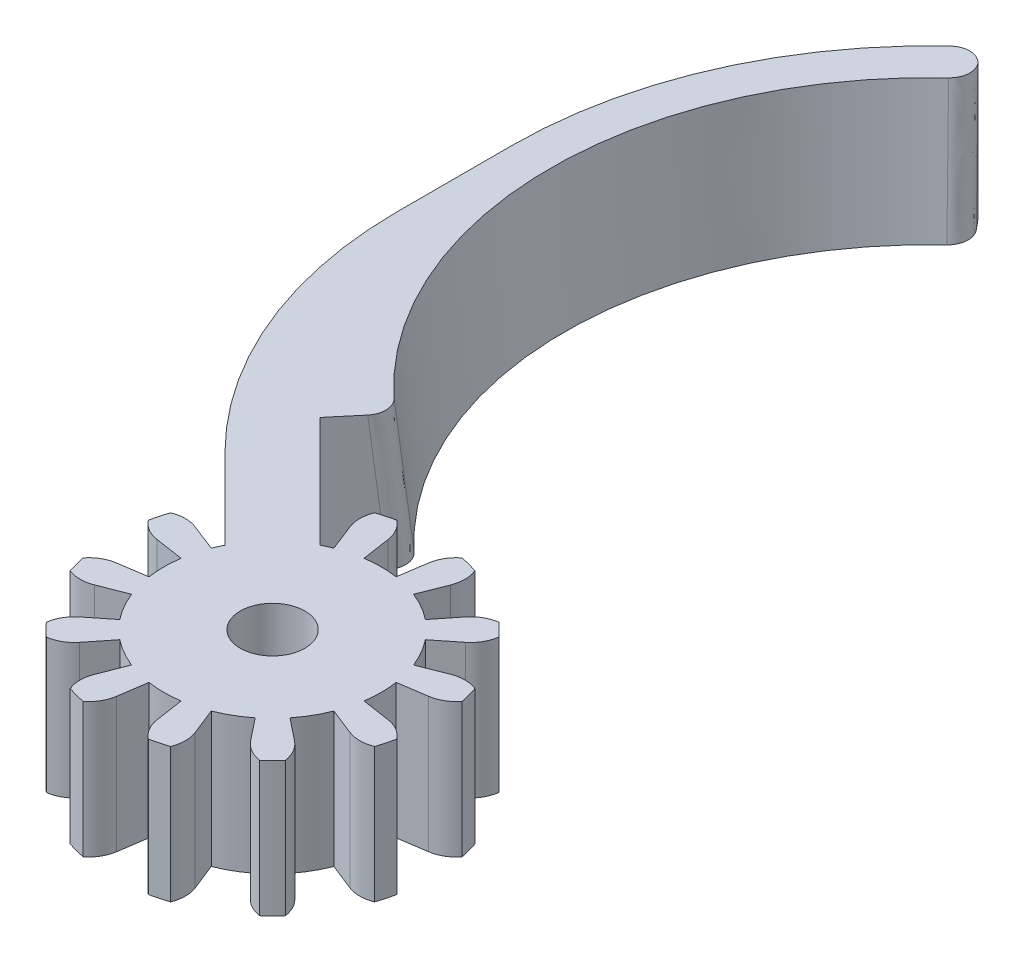
SolidWorks part; units mm, degrees
ref_plane "Plan de face" through (0, 0, 0) normal (0, 0, 1) x (1, 0, 0)
ref_plane "Plan de dessus" through (0, 0, 0) normal (0, 1, 0) x (1, 0, 0)
ref_plane "Plan de droite" through (0, 0, 0) normal (1, 0, 0) x (0, 0, -1)
sketch "Esquisse1" plane through (0, 0, 0) normal (0, 1, 0) x (1, 0, 0)
  line L0 (0, 0) -> (0, 27.3284) construction
  line L1 (-38.1202, 0) -> (19.7056, 0) construction
  line L2 (8.75, 40) -> (-53.1888, 40) construction
  line L3 (8.75, 40) -> (-13.9541, 12.9423) construction
  line L4 (8.75, 40) -> (-15.7208, 69.1632) construction
  line L5 (-22.25, 47.3971) -> (-22.25, -30.6529) construction
  line L6 (0, 0) -> (-33.9162, 33.9162) construction
  line L7 (-13.1703, 9.6348) -> (-7.1971, 3.6616)
  line L8 (-11.8794, 15.4149) -> (-3.6616, 7.1971)
  line L9 (-22.25, 40) -> (-22.25, 31.5551)
  line L10 (0, 0) -> (3.5575, 13.2769) construction
  line L11 (0, 0) -> (7.0447, 12.2018) construction
  line L12 (0, 0) -> (4.3209, 13.1034) construction
  line L13 (0, 0) -> (5.1162, 12.9881) construction
  line L14 (3.7383, 9.4903) -> (2.9595, 7.5131)
  line L15 (1.5077, 10.088) -> (1.1936, 7.9863)
  line L16 (6.3496, 7.9826) -> (5.0268, 6.3196)
  line L17 (7.9826, 6.3496) -> (6.3196, 5.0268)
  line L18 (9.4903, 3.7383) -> (7.5131, 2.9595)
  line L19 (10.088, 1.5077) -> (7.9863, 1.1936)
  line L20 (10.088, -1.5077) -> (7.9863, -1.1936)
  line L21 (9.4903, -3.7383) -> (7.5131, -2.9595)
  line L22 (7.9826, -6.3496) -> (6.3196, -5.0268)
  line L23 (6.3496, -7.9826) -> (5.0268, -6.3196)
  line L24 (3.7383, -9.4903) -> (2.9595, -7.5131)
  line L25 (1.5077, -10.088) -> (1.1936, -7.9863)
  line L26 (-1.5077, -10.088) -> (-1.1936, -7.9863)
  line L27 (-3.7383, -9.4903) -> (-2.9595, -7.5131)
  line L28 (-6.3496, -7.9826) -> (-5.0268, -6.3196)
  line L29 (-7.9826, -6.3496) -> (-6.3196, -5.0268)
  line L30 (-9.4903, -3.7383) -> (-7.5131, -2.9595)
  line L31 (-10.088, -1.5077) -> (-7.9863, -1.1936)
  line L32 (-10.088, 1.5077) -> (-7.9863, 1.1936)
  line L33 (-9.4903, 3.7383) -> (-7.5131, 2.9595)
  line L34 (-17.25, 40) -> (-17.25, -30.6529) construction
  line L36 (-3.7383, 9.4903) -> (-2.9595, 7.5131)
  line L37 (-1.5077, 10.088) -> (-1.1936, 7.9863)
  line L38 (-7.9826, 6.3496) -> (-6.3196, 5.0268) [skipped]
  line L39 (-6.3496, 7.9826) -> (-5.0268, 6.3196) [skipped]
  line L40 (-11.8794, 15.4149) -> (-7.9625, 20.0828)
  line L41 (-10.1877, 62.5691) -> (-7.9625, 59.9172)
  line L42 (8.75, 40) -> (8.75, 0) construction
  circle A0 centre (0, 0) radius 11.9 construction
  circle A1 centre (0, 0) radius 10.2 construction
  circle A2 centre (0, 0) radius 8.075 construction
  circle A3 centre (8.75, 40) radius 25 construction
  arc A4 (-7.9625, 59.9172) -> (-7.9625, 20.0828) centre (8.75, 40) ccw
  arc A5 (-22.25, 40) -> (-12.3581, 62.7035) centre (8.75, 40) cw
  arc A7 (3.7266, 11.3014) -> (3.7383, 9.4903) centre (1.4762, 10.3813) cw
  arc A8 (3.7266, 11.3014) -> (2.4233, 11.6506) centre (0, 0) ccw
  arc A9 (4.0375, 6.9932) -> (2.9595, 7.5131) centre (0, 0) ccw
  arc A10 (0, 8.075) -> (1.1936, 7.9863) centre (0, 0) cw
  arc A11 (2.4233, 11.6506) -> (1.5077, 10.088) centre (3.9122, 9.7286) ccw
  arc A12 (4.0375, 6.9932) -> (5.0268, 6.3196) centre (0, 0) cw
  arc A13 (7.924, 8.8781) -> (6.3496, 7.9826) centre (8.2524, 6.4691) ccw
  arc A14 (8.8781, 7.924) -> (7.924, 8.8781) centre (0, 0) ccw
  arc A15 (8.8781, 7.924) -> (7.9826, 6.3496) centre (6.4691, 8.2524) cw
  arc A16 (6.9932, 4.0375) -> (6.3196, 5.0268) centre (0, 0) ccw
  arc A17 (6.9932, 4.0375) -> (7.5131, 2.9595) centre (0, 0) cw
  arc A18 (11.3014, 3.7266) -> (9.4903, 3.7383) centre (10.3813, 1.4762) ccw
  arc A19 (11.6506, 2.4233) -> (11.3014, 3.7266) centre (0, 0) ccw
  arc A20 (11.6506, 2.4233) -> (10.088, 1.5077) centre (9.7286, 3.9122) cw
  arc A21 (8.075, 0) -> (7.9863, 1.1936) centre (0, 0) ccw
  arc A22 (8.075, 0) -> (7.9863, -1.1936) centre (0, 0) cw
  arc A23 (11.6506, -2.4233) -> (10.088, -1.5077) centre (9.7286, -3.9122) ccw
  arc A24 (11.3014, -3.7266) -> (11.6506, -2.4233) centre (0, 0) ccw
  arc A25 (11.3014, -3.7266) -> (9.4903, -3.7383) centre (10.3813, -1.4762) cw
  arc A26 (6.9932, -4.0375) -> (7.5131, -2.9595) centre (0, 0) ccw
  arc A27 (6.9932, -4.0375) -> (6.3196, -5.0268) centre (0, 0) cw
  arc A28 (8.8781, -7.924) -> (7.9826, -6.3496) centre (6.4691, -8.2524) ccw
  arc A29 (7.924, -8.8781) -> (8.8781, -7.924) centre (0, 0) ccw
  arc A30 (7.924, -8.8781) -> (6.3496, -7.9826) centre (8.2524, -6.4691) cw
  arc A31 (4.0375, -6.9932) -> (5.0268, -6.3196) centre (0, 0) ccw
  arc A32 (4.0375, -6.9932) -> (2.9595, -7.5131) centre (0, 0) cw
  arc A33 (3.7266, -11.3014) -> (3.7383, -9.4903) centre (1.4762, -10.3813) ccw
  arc A34 (2.4233, -11.6506) -> (3.7266, -11.3014) centre (0, 0) ccw
  arc A35 (2.4233, -11.6506) -> (1.5077, -10.088) centre (3.9122, -9.7286) cw
  arc A36 (0, -8.075) -> (1.1936, -7.9863) centre (0, 0) ccw
  arc A37 (0, -8.075) -> (-1.1936, -7.9863) centre (0, 0) cw
  arc A38 (-2.4233, -11.6506) -> (-1.5077, -10.088) centre (-3.9122, -9.7286) ccw
  arc A39 (-3.7266, -11.3014) -> (-2.4233, -11.6506) centre (0, 0) ccw
  arc A40 (-3.7266, -11.3014) -> (-3.7383, -9.4903) centre (-1.4762, -10.3813) cw
  arc A41 (-4.0375, -6.9932) -> (-2.9595, -7.5131) centre (0, 0) ccw
  arc A42 (-4.0375, -6.9932) -> (-5.0268, -6.3196) centre (0, 0) cw
  arc A43 (-7.924, -8.8781) -> (-6.3496, -7.9826) centre (-8.2524, -6.4691) ccw
  arc A44 (-8.8781, -7.924) -> (-7.924, -8.8781) centre (0, 0) ccw
  arc A45 (-8.8781, -7.924) -> (-7.9826, -6.3496) centre (-6.4691, -8.2524) cw
  arc A46 (-6.9932, -4.0375) -> (-6.3196, -5.0268) centre (0, 0) ccw
  arc A47 (-6.9932, -4.0375) -> (-7.5131, -2.9595) centre (0, 0) cw
  arc A48 (-11.3014, -3.7266) -> (-9.4903, -3.7383) centre (-10.3813, -1.4762) ccw
  arc A49 (-11.6506, -2.4233) -> (-11.3014, -3.7266) centre (0, 0) ccw
  arc A50 (-11.6506, -2.4233) -> (-10.088, -1.5077) centre (-9.7286, -3.9122) cw
  arc A51 (-8.075, 0) -> (-7.9863, -1.1936) centre (0, 0) ccw
  arc A52 (-8.075, 0) -> (-7.9863, 1.1936) centre (0, 0) cw
  arc A53 (-11.6506, 2.4233) -> (-10.088, 1.5077) centre (-9.7286, 3.9122) ccw
  arc A54 (-11.3014, 3.7266) -> (-11.6506, 2.4233) centre (0, 0) ccw
  arc A55 (-11.3014, 3.7266) -> (-9.4903, 3.7383) centre (-10.3813, 1.4762) cw
  arc A56 (-2.9595, 7.5131) -> (-3.6616, 7.1971) centre (0, 0) ccw
  arc A57 (-7.5131, 2.9595) -> (-7.1971, 3.6616) centre (0, 0) cw
  arc A60 (-13.1703, 9.6348) -> (-22.25, 31.5551) centre (8.75, 31.5551) cw
  arc A61 (-12.3581, 62.7035) -> (-10.1877, 62.5691) centre (-11.3368, 61.6049) cw
  arc A63 (-3.7266, 11.3014) -> (-3.7383, 9.4903) centre (-1.4762, 10.3813) ccw
  arc A64 (-2.4233, 11.6506) -> (-3.7266, 11.3014) centre (0, 0) ccw
  arc A65 (-2.4233, 11.6506) -> (-1.5077, 10.088) centre (-3.9122, 9.7286) cw
  arc A66 (0, 8.075) -> (-1.1936, 7.9863) centre (0, 0) ccw
  arc A67 (-8.8781, 7.924) -> (-7.9826, 6.3496) centre (-6.4691, 8.2524) ccw [skipped]
  arc A68 (-7.924, 8.8781) -> (-8.8781, 7.924) centre (0, 0) ccw [skipped]
  arc A69 (-7.924, 8.8781) -> (-6.3496, 7.9826) centre (-8.2524, 6.4691) cw [skipped]
  arc A70 (-6.9932, 4.0375) -> (-6.3196, 5.0268) centre (0, 0) cw [skipped]
  arc A71 (-4.0375, 6.9932) -> (-5.0268, 6.3196) centre (0, 0) ccw [skipped]
  arc A72 (-4.0375, 6.9932) -> (-2.9595, 7.5131) centre (0, 0) cw [skipped]
  arc A73 (-6.9932, 4.0375) -> (-7.5131, 2.9595) centre (0, 0) ccw [skipped]
  point P72 (0, 0)
  point P135 (-17.25, 20.2855)
  point P138 (-22.25, 18.7145)
  point P155 (-11.1764, 63.7474)
  point P169 (-10.855, 16.6356)
  point P176 (-17.25, 23.2668)
  dimension "D1" = 50
  dimension "D2" = 50
  dimension "D5" = 20.4
  dimension "D6" = 23.8
  dimension "D7" = 16.15
  dimension "D11" = 26
  dimension "D12" = 5
  dimension "D17" = 12
  dimension "D18" = 5
  dimension "D20" = 1.5
  dimension "D3" = 40
  dimension "D4" = 50
  dimension "D9" = 45
  dimension "D10" = 5
  dimension "D13" = 8.75
  dimension "D14" = 3.25
  dimension "D15" = 6.5
  dimension "D16" = 15
extrude "Boss.-Extru.1" add sketch "Esquisse1" along normal blind 10
chamfer "Chanfrein1" distance 20 angle 6.03 1 edges at (-17.25, 10, -40)
fillet "Congé1" radius 1.5 2 edges at (-8.981, 5, -61.131) (-8.981, 5, -18.869)
sketch "Esquisse3" plane through (0, 10, 0) normal (0, 1, 0) x (1, 0, 0)
  line L26 (-22.25, 40) -> (-22.25, 31.5551)
  line L27 (-13.1703, 9.6348) -> (-7.1971, 3.6616)
  line L28 (-7.5131, 2.9595) -> (-9.4903, 3.7383)
  line L29 (-10.088, 1.5077) -> (-7.9863, 1.1936)
  line L30 (-7.9863, -1.1936) -> (-10.088, -1.5077)
  line L31 (-9.4903, -3.7383) -> (-7.5131, -2.9595)
  line L32 (-6.3196, -5.0268) -> (-7.9826, -6.3496)
  line L33 (-6.3496, -7.9826) -> (-5.0268, -6.3196)
  line L34 (-2.9595, -7.5131) -> (-3.7383, -9.4903)
  line L35 (-1.5077, -10.088) -> (-1.1936, -7.9863)
  line L36 (1.1936, -7.9863) -> (1.5077, -10.088)
  line L37 (3.7383, -9.4903) -> (2.9595, -7.5131)
  line L38 (5.0268, -6.3196) -> (6.3496, -7.9826)
  line L39 (7.9826, -6.3496) -> (6.3196, -5.0268)
  line L40 (7.5131, -2.9595) -> (9.4903, -3.7383)
  line L41 (10.088, -1.5077) -> (7.9863, -1.1936)
  line L42 (7.9863, 1.1936) -> (10.088, 1.5077)
  line L43 (9.4903, 3.7383) -> (7.5131, 2.9595)
  line L44 (6.3196, 5.0268) -> (7.9826, 6.3496)
  line L45 (6.3496, 7.9826) -> (5.0268, 6.3196)
  line L46 (2.9595, 7.5131) -> (3.7383, 9.4903)
  line L47 (1.5077, 10.088) -> (1.1936, 7.9863)
  line L48 (-1.1936, 7.9863) -> (-1.5077, 10.088)
  line L49 (-3.7383, 9.4903) -> (-2.9595, 7.5131)
  line L50 (-3.6616, 7.1971) -> (-11.8794, 15.4149)
  line L51 (-11.8794, 15.4149) -> (-10.2656, 17.3381)
  line L52 (-22.25, 40) -> (-22.25, 31.5551)
  line L53 (-13.1703, 9.6348) -> (-7.1971, 3.6616)
  line L54 (-7.5131, 2.9595) -> (-9.4903, 3.7383)
  line L55 (-10.088, 1.5077) -> (-7.9863, 1.1936)
  line L56 (-7.9863, -1.1936) -> (-10.088, -1.5077)
  line L57 (-9.4903, -3.7383) -> (-7.5131, -2.9595)
  line L58 (-6.3196, -5.0268) -> (-7.9826, -6.3496)
  line L59 (-6.3496, -7.9826) -> (-5.0268, -6.3196)
  line L60 (-2.9595, -7.5131) -> (-3.7383, -9.4903)
  line L61 (-1.5077, -10.088) -> (-1.1936, -7.9863)
  line L62 (1.1936, -7.9863) -> (1.5077, -10.088)
  line L63 (3.7383, -9.4903) -> (2.9595, -7.5131)
  line L64 (5.0268, -6.3196) -> (6.3496, -7.9826)
  line L65 (7.9826, -6.3496) -> (6.3196, -5.0268)
  line L66 (7.5131, -2.9595) -> (9.4903, -3.7383)
  line L67 (10.088, -1.5077) -> (7.9863, -1.1936)
  line L68 (7.9863, 1.1936) -> (10.088, 1.5077)
  line L69 (9.4903, 3.7383) -> (7.5131, 2.9595)
  line L70 (6.3196, 5.0268) -> (7.9826, 6.3496)
  line L71 (6.3496, 7.9826) -> (5.0268, 6.3196)
  line L72 (2.9595, 7.5131) -> (3.7383, 9.4903)
  line L73 (1.5077, 10.088) -> (1.1936, 7.9863)
  line L74 (-1.1936, 7.9863) -> (-1.5077, 10.088)
  line L75 (-3.7383, 9.4903) -> (-2.9595, 7.5131)
  line L76 (-3.6616, 7.1971) -> (-11.8794, 15.4149)
  line L77 (-11.8794, 15.4149) -> (-10.2656, 17.3381)
  circle A0 centre (0, 0) radius 2.4
  arc A49 (-10.3884, 60.5923) -> (-10.3884, 19.4077) centre (8.75, 40) ccw
  arc A50 (-10.2275, 62.6146) -> (-12.3581, 62.7035) centre (-11.3368, 61.6049) ccw
  arc A51 (-12.3581, 62.7035) -> (-22.25, 40) centre (8.75, 40) ccw
  arc A52 (-22.25, 31.5551) -> (-13.1703, 9.6348) centre (8.75, 31.5551) ccw
  arc A53 (-7.1971, 3.6616) -> (-7.5131, 2.9595) centre (0, 0) ccw
  arc A54 (-9.4903, 3.7383) -> (-11.3014, 3.7266) centre (-10.3813, 1.4762) ccw
  arc A55 (-11.3014, 3.7266) -> (-11.6506, 2.4233) centre (0, 0) ccw
  arc A56 (-11.6506, 2.4233) -> (-10.088, 1.5077) centre (-9.7286, 3.9122) ccw
  arc A57 (-7.9863, 1.1936) -> (-7.9863, -1.1936) centre (0, 0) ccw
  arc A58 (-10.088, -1.5077) -> (-11.6506, -2.4233) centre (-9.7286, -3.9122) ccw
  arc A59 (-11.6506, -2.4233) -> (-11.3014, -3.7266) centre (0, 0) ccw
  arc A60 (-11.3014, -3.7266) -> (-9.4903, -3.7383) centre (-10.3813, -1.4762) ccw
  arc A61 (-7.5131, -2.9595) -> (-6.3196, -5.0268) centre (0, 0) ccw
  arc A62 (-7.9826, -6.3496) -> (-8.8781, -7.924) centre (-6.4691, -8.2524) ccw
  arc A63 (-8.8781, -7.924) -> (-7.924, -8.8781) centre (0, 0) ccw
  arc A64 (-7.924, -8.8781) -> (-6.3496, -7.9826) centre (-8.2524, -6.4691) ccw
  arc A65 (-5.0268, -6.3196) -> (-2.9595, -7.5131) centre (0, 0) ccw
  arc A66 (-3.7383, -9.4903) -> (-3.7266, -11.3014) centre (-1.4762, -10.3813) ccw
  arc A67 (-3.7266, -11.3014) -> (-2.4233, -11.6506) centre (0, 0) ccw
  arc A68 (-2.4233, -11.6506) -> (-1.5077, -10.088) centre (-3.9122, -9.7286) ccw
  arc A69 (-1.1936, -7.9863) -> (1.1936, -7.9863) centre (0, 0) ccw
  arc A70 (1.5077, -10.088) -> (2.4233, -11.6506) centre (3.9122, -9.7286) ccw
  arc A71 (2.4233, -11.6506) -> (3.7266, -11.3014) centre (0, 0) ccw
  arc A72 (3.7266, -11.3014) -> (3.7383, -9.4903) centre (1.4762, -10.3813) ccw
  arc A73 (2.9595, -7.5131) -> (5.0268, -6.3196) centre (0, 0) ccw
  arc A74 (6.3496, -7.9826) -> (7.924, -8.8781) centre (8.2524, -6.4691) ccw
  arc A75 (7.924, -8.8781) -> (8.8781, -7.924) centre (0, 0) ccw
  arc A76 (8.8781, -7.924) -> (7.9826, -6.3496) centre (6.4691, -8.2524) ccw
  arc A77 (6.3196, -5.0268) -> (7.5131, -2.9595) centre (0, 0) ccw
  arc A78 (9.4903, -3.7383) -> (11.3014, -3.7266) centre (10.3813, -1.4762) ccw
  arc A79 (11.3014, -3.7266) -> (11.6506, -2.4233) centre (0, 0) ccw
  arc A80 (11.6506, -2.4233) -> (10.088, -1.5077) centre (9.7286, -3.9122) ccw
  arc A81 (7.9863, -1.1936) -> (7.9863, 1.1936) centre (0, 0) ccw
  arc A82 (10.088, 1.5077) -> (11.6506, 2.4233) centre (9.7286, 3.9122) ccw
  arc A83 (11.6506, 2.4233) -> (11.3014, 3.7266) centre (0, 0) ccw
  arc A84 (11.3014, 3.7266) -> (9.4903, 3.7383) centre (10.3813, 1.4762) ccw
  arc A85 (7.5131, 2.9595) -> (6.3196, 5.0268) centre (0, 0) ccw
  arc A86 (7.9826, 6.3496) -> (8.8781, 7.924) centre (6.4691, 8.2524) ccw
  arc A87 (8.8781, 7.924) -> (7.924, 8.8781) centre (0, 0) ccw
  arc A88 (7.924, 8.8781) -> (6.3496, 7.9826) centre (8.2524, 6.4691) ccw
  arc A89 (5.0268, 6.3196) -> (2.9595, 7.5131) centre (0, 0) ccw
  arc A90 (3.7383, 9.4903) -> (3.7266, 11.3014) centre (1.4762, 10.3813) ccw
  arc A91 (3.7266, 11.3014) -> (2.4233, 11.6506) centre (0, 0) ccw
  arc A92 (2.4233, 11.6506) -> (1.5077, 10.088) centre (3.9122, 9.7286) ccw
  arc A93 (1.1936, 7.9863) -> (-1.1936, 7.9863) centre (0, 0) ccw
  arc A94 (-1.5077, 10.088) -> (-2.4233, 11.6506) centre (-3.9122, 9.7286) ccw
  arc A95 (-2.4233, 11.6506) -> (-3.7266, 11.3014) centre (0, 0) ccw
  arc A96 (-3.7266, 11.3014) -> (-3.7383, 9.4903) centre (-1.4762, 10.3813) ccw
  arc A97 (-2.9595, 7.5131) -> (-3.6616, 7.1971) centre (0, 0) ccw
  arc A98 (-10.3884, 60.5923) -> (-10.3884, 19.4077) centre (8.75, 40) ccw
  arc A99 (-10.2275, 62.6146) -> (-12.3581, 62.7035) centre (-11.3368, 61.6049) ccw
  arc A100 (-12.3581, 62.7035) -> (-22.25, 40) centre (8.75, 40) ccw
  arc A101 (-22.25, 31.5551) -> (-13.1703, 9.6348) centre (8.75, 31.5551) ccw
  arc A102 (-7.1971, 3.6616) -> (-7.5131, 2.9595) centre (0, 0) ccw
  arc A103 (-9.4903, 3.7383) -> (-11.3014, 3.7266) centre (-10.3813, 1.4762) ccw
  arc A104 (-11.3014, 3.7266) -> (-11.6506, 2.4233) centre (0, 0) ccw
  arc A105 (-11.6506, 2.4233) -> (-10.088, 1.5077) centre (-9.7286, 3.9122) ccw
  arc A106 (-7.9863, 1.1936) -> (-7.9863, -1.1936) centre (0, 0) ccw
  arc A107 (-10.088, -1.5077) -> (-11.6506, -2.4233) centre (-9.7286, -3.9122) ccw
  arc A108 (-11.6506, -2.4233) -> (-11.3014, -3.7266) centre (0, 0) ccw
  arc A109 (-11.3014, -3.7266) -> (-9.4903, -3.7383) centre (-10.3813, -1.4762) ccw
  arc A110 (-7.5131, -2.9595) -> (-6.3196, -5.0268) centre (0, 0) ccw
  arc A111 (-7.9826, -6.3496) -> (-8.8781, -7.924) centre (-6.4691, -8.2524) ccw
  arc A112 (-8.8781, -7.924) -> (-7.924, -8.8781) centre (0, 0) ccw
  arc A113 (-7.924, -8.8781) -> (-6.3496, -7.9826) centre (-8.2524, -6.4691) ccw
  arc A114 (-5.0268, -6.3196) -> (-2.9595, -7.5131) centre (0, 0) ccw
  arc A115 (-3.7383, -9.4903) -> (-3.7266, -11.3014) centre (-1.4762, -10.3813) ccw
  arc A116 (-3.7266, -11.3014) -> (-2.4233, -11.6506) centre (0, 0) ccw
  arc A117 (-2.4233, -11.6506) -> (-1.5077, -10.088) centre (-3.9122, -9.7286) ccw
  arc A118 (-1.1936, -7.9863) -> (1.1936, -7.9863) centre (0, 0) ccw
  arc A119 (1.5077, -10.088) -> (2.4233, -11.6506) centre (3.9122, -9.7286) ccw
  arc A120 (2.4233, -11.6506) -> (3.7266, -11.3014) centre (0, 0) ccw
  arc A121 (3.7266, -11.3014) -> (3.7383, -9.4903) centre (1.4762, -10.3813) ccw
  arc A122 (2.9595, -7.5131) -> (5.0268, -6.3196) centre (0, 0) ccw
  arc A123 (6.3496, -7.9826) -> (7.924, -8.8781) centre (8.2524, -6.4691) ccw
  arc A124 (7.924, -8.8781) -> (8.8781, -7.924) centre (0, 0) ccw
  arc A125 (8.8781, -7.924) -> (7.9826, -6.3496) centre (6.4691, -8.2524) ccw
  arc A126 (6.3196, -5.0268) -> (7.5131, -2.9595) centre (0, 0) ccw
  arc A127 (9.4903, -3.7383) -> (11.3014, -3.7266) centre (10.3813, -1.4762) ccw
  arc A128 (11.3014, -3.7266) -> (11.6506, -2.4233) centre (0, 0) ccw
  arc A129 (11.6506, -2.4233) -> (10.088, -1.5077) centre (9.7286, -3.9122) ccw
  arc A130 (7.9863, -1.1936) -> (7.9863, 1.1936) centre (0, 0) ccw
  arc A131 (10.088, 1.5077) -> (11.6506, 2.4233) centre (9.7286, 3.9122) ccw
  arc A132 (11.6506, 2.4233) -> (11.3014, 3.7266) centre (0, 0) ccw
  arc A133 (11.3014, 3.7266) -> (9.4903, 3.7383) centre (10.3813, 1.4762) ccw
  arc A134 (7.5131, 2.9595) -> (6.3196, 5.0268) centre (0, 0) ccw
  arc A135 (7.9826, 6.3496) -> (8.8781, 7.924) centre (6.4691, 8.2524) ccw
  arc A136 (8.8781, 7.924) -> (7.924, 8.8781) centre (0, 0) ccw
  arc A137 (7.924, 8.8781) -> (6.3496, 7.9826) centre (8.2524, 6.4691) ccw
  arc A138 (5.0268, 6.3196) -> (2.9595, 7.5131) centre (0, 0) ccw
  arc A139 (3.7383, 9.4903) -> (3.7266, 11.3014) centre (1.4762, 10.3813) ccw
  arc A140 (3.7266, 11.3014) -> (2.4233, 11.6506) centre (0, 0) ccw
  arc A141 (2.4233, 11.6506) -> (1.5077, 10.088) centre (3.9122, 9.7286) ccw
  arc A142 (1.1936, 7.9863) -> (-1.1936, 7.9863) centre (0, 0) ccw
  arc A143 (-1.5077, 10.088) -> (-2.4233, 11.6506) centre (-3.9122, 9.7286) ccw
  arc A144 (-2.4233, 11.6506) -> (-3.7266, 11.3014) centre (0, 0) ccw
  arc A145 (-3.7266, 11.3014) -> (-3.7383, 9.4903) centre (-1.4762, 10.3813) ccw
  arc A146 (-2.9595, 7.5131) -> (-3.6616, 7.1971) centre (0, 0) ccw
  spline S2 degree 3 poles (904.1768, 2910.4144) (-208.0871, 144.2381) (-16.4538, 47.7772) (-10.0195, 61.1214) (-9.9874, 61.208) (-9.9391, 61.3864) (-9.9231, 61.4792) (-8.9721, 73.586) (-156.7275, 93.4089) (359.3029, -2911.4528) knots -19.517492 -19.517492 -19.517492 -19.517492 0.25 0.25 0.375 0.375 0.5 0.5 16.747829 16.747829 16.747829 16.747829 only from (-10.3884, 60.5923) to (-10.2275, 62.6146)
  spline S3 degree 3 poles (652.1757, 2936.6854) (-207.8805, 69.6069) (-14.5415, 4.1362) (-9.9582, 17.9249) (-9.9369, 18.0173) (-9.9119, 18.2055) (-9.9082, 18.3023) (-9.9192, 18.4923) (-9.9335, 18.5859) (-9.9802, 18.7706) (-10.0127, 18.8618) (-14.9397, 29.3716) (-143.2098, -13.6236) (1107.06, -2761.596) knots -18.632107 -18.632107 -18.632107 -18.632107 0.25 0.25 0.375 0.375 0.5 0.5 0.625 0.625 0.75 0.75 15.917753 15.917753 15.917753 15.917753 only from (-10.2656, 17.3381) to (-10.3884, 19.4077)
  spline S4 degree 3 poles (-10.3884, 60.5923) (-10.2513, 60.7197) (-10.1408, 60.8699) (-10.0195, 61.1214) (-9.9874, 61.208) (-9.9391, 61.3864) (-9.9231, 61.4792) (-9.8868, 61.9413) (-9.9986, 62.3184) (-10.2275, 62.6146) knots 0 0 0 0 0.25 0.25 0.375 0.375 0.5 0.5 1 1 1 1
  spline S5 degree 3 poles (-10.2656, 17.3381) (-10.142, 17.4854) (-10.0486, 17.6529) (-9.9582, 17.9249) (-9.9369, 18.0173) (-9.9119, 18.2055) (-9.9082, 18.3023) (-9.9192, 18.4923) (-9.9335, 18.5859) (-9.9802, 18.7706) (-10.0127, 18.8618) (-10.1335, 19.1195) (-10.2476, 19.2768) (-10.3884, 19.4077) knots 0 0 0 0 0.25 0.25 0.375 0.375 0.5 0.5 0.625 0.625 0.75 0.75 1 1 1 1
  dimension "D2" = 4.8
  dimension "D1" = 0
extrude "Enlèv. mat.-Extru.1" cut sketch "Esquisse3" against normal blind 4 contours A0
sketch "Esquisse4" plane through (0, 0, 0) normal (0, -1, 0) x (1, 0, 0)
  line L26 (-9.5857, -18.1484) -> (-11.8794, -15.4149)
  line L27 (-11.8794, -15.4149) -> (-3.6616, -7.1971)
  line L28 (-2.9595, -7.5131) -> (-3.7383, -9.4903)
  line L29 (-1.5077, -10.088) -> (-1.1936, -7.9863)
  line L30 (1.1936, -7.9863) -> (1.5077, -10.088)
  line L31 (3.7383, -9.4903) -> (2.9595, -7.5131)
  line L32 (5.0268, -6.3196) -> (6.3496, -7.9826)
  line L33 (7.9826, -6.3496) -> (6.3196, -5.0268)
  line L34 (7.5131, -2.9595) -> (9.4903, -3.7383)
  line L35 (10.088, -1.5077) -> (7.9863, -1.1936)
  line L36 (7.9863, 1.1936) -> (10.088, 1.5077)
  line L37 (9.4903, 3.7383) -> (7.5131, 2.9595)
  line L38 (6.3196, 5.0268) -> (7.9826, 6.3496)
  line L39 (6.3496, 7.9826) -> (5.0268, 6.3196)
  line L40 (2.9595, 7.5131) -> (3.7383, 9.4903)
  line L41 (1.5077, 10.088) -> (1.1936, 7.9863)
  line L42 (-1.1936, 7.9863) -> (-1.5077, 10.088)
  line L43 (-3.7383, 9.4903) -> (-2.9595, 7.5131)
  line L44 (-5.0268, 6.3196) -> (-6.3496, 7.9826)
  line L45 (-7.9826, 6.3496) -> (-6.3196, 5.0268)
  line L46 (-7.5131, 2.9595) -> (-9.4903, 3.7383)
  line L47 (-10.088, 1.5077) -> (-7.9863, 1.1936)
  line L48 (-7.9863, -1.1936) -> (-10.088, -1.5077)
  line L49 (-9.4903, -3.7383) -> (-7.5131, -2.9595)
  line L50 (-7.1971, -3.6616) -> (-13.1703, -9.6348)
  line L51 (-22.25, -31.5551) -> (-22.25, -40)
  line L52 (-9.5857, -18.1484) -> (-11.8794, -15.4149)
  line L53 (-11.8794, -15.4149) -> (-3.6616, -7.1971)
  line L54 (-2.9595, -7.5131) -> (-3.7383, -9.4903)
  line L55 (-1.5077, -10.088) -> (-1.1936, -7.9863)
  line L56 (1.1936, -7.9863) -> (1.5077, -10.088)
  line L57 (3.7383, -9.4903) -> (2.9595, -7.5131)
  line L58 (5.0268, -6.3196) -> (6.3496, -7.9826)
  line L59 (7.9826, -6.3496) -> (6.3196, -5.0268)
  line L60 (7.5131, -2.9595) -> (9.4903, -3.7383)
  line L61 (10.088, -1.5077) -> (7.9863, -1.1936)
  line L62 (7.9863, 1.1936) -> (10.088, 1.5077)
  line L63 (9.4903, 3.7383) -> (7.5131, 2.9595)
  line L64 (6.3196, 5.0268) -> (7.9826, 6.3496)
  line L65 (6.3496, 7.9826) -> (5.0268, 6.3196)
  line L66 (2.9595, 7.5131) -> (3.7383, 9.4903)
  line L67 (1.5077, 10.088) -> (1.1936, 7.9863)
  line L68 (-1.1936, 7.9863) -> (-1.5077, 10.088)
  line L69 (-3.7383, 9.4903) -> (-2.9595, 7.5131)
  line L70 (-5.0268, 6.3196) -> (-6.3496, 7.9826)
  line L71 (-7.9826, 6.3496) -> (-6.3196, 5.0268)
  line L72 (-7.5131, 2.9595) -> (-9.4903, 3.7383)
  line L73 (-10.088, 1.5077) -> (-7.9863, 1.1936)
  line L74 (-7.9863, -1.1936) -> (-10.088, -1.5077)
  line L75 (-9.4903, -3.7383) -> (-7.5131, -2.9595)
  line L76 (-7.1971, -3.6616) -> (-13.1703, -9.6348)
  line L77 (-22.25, -31.5551) -> (-22.25, -40)
  line L79 (-10.1877, -62.5691) -> (-9.5857, -61.8516)
  line L80 (-10.1877, -62.5691) -> (-9.5857, -61.8516)
  circle A0 centre (0, 0) radius 4
  arc A47 (-9.7065, -20.2161) -> (-9.7065, -59.7839) centre (8.75, -40) ccw
  arc A48 (-3.6616, -7.1971) -> (-2.9595, -7.5131) centre (0, 0) ccw
  arc A49 (-3.7383, -9.4903) -> (-3.7266, -11.3014) centre (-1.4762, -10.3813) ccw
  arc A50 (-3.7266, -11.3014) -> (-2.4233, -11.6506) centre (0, 0) ccw
  arc A51 (-2.4233, -11.6506) -> (-1.5077, -10.088) centre (-3.9122, -9.7286) ccw
  arc A52 (-1.1936, -7.9863) -> (1.1936, -7.9863) centre (0, 0) ccw
  arc A53 (1.5077, -10.088) -> (2.4233, -11.6506) centre (3.9122, -9.7286) ccw
  arc A54 (2.4233, -11.6506) -> (3.7266, -11.3014) centre (0, 0) ccw
  arc A55 (3.7266, -11.3014) -> (3.7383, -9.4903) centre (1.4762, -10.3813) ccw
  arc A56 (2.9595, -7.5131) -> (5.0268, -6.3196) centre (0, 0) ccw
  arc A57 (6.3496, -7.9826) -> (7.924, -8.8781) centre (8.2524, -6.4691) ccw
  arc A58 (7.924, -8.8781) -> (8.8781, -7.924) centre (0, 0) ccw
  arc A59 (8.8781, -7.924) -> (7.9826, -6.3496) centre (6.4691, -8.2524) ccw
  arc A60 (6.3196, -5.0268) -> (7.5131, -2.9595) centre (0, 0) ccw
  arc A61 (9.4903, -3.7383) -> (11.3014, -3.7266) centre (10.3813, -1.4762) ccw
  arc A62 (11.3014, -3.7266) -> (11.6506, -2.4233) centre (0, 0) ccw
  arc A63 (11.6506, -2.4233) -> (10.088, -1.5077) centre (9.7286, -3.9122) ccw
  arc A64 (7.9863, -1.1936) -> (7.9863, 1.1936) centre (0, 0) ccw
  arc A65 (10.088, 1.5077) -> (11.6506, 2.4233) centre (9.7286, 3.9122) ccw
  arc A66 (11.6506, 2.4233) -> (11.3014, 3.7266) centre (0, 0) ccw
  arc A67 (11.3014, 3.7266) -> (9.4903, 3.7383) centre (10.3813, 1.4762) ccw
  arc A68 (7.5131, 2.9595) -> (6.3196, 5.0268) centre (0, 0) ccw
  arc A69 (7.9826, 6.3496) -> (8.8781, 7.924) centre (6.4691, 8.2524) ccw
  arc A70 (8.8781, 7.924) -> (7.924, 8.8781) centre (0, 0) ccw
  arc A71 (7.924, 8.8781) -> (6.3496, 7.9826) centre (8.2524, 6.4691) ccw
  arc A72 (5.0268, 6.3196) -> (2.9595, 7.5131) centre (0, 0) ccw
  arc A73 (3.7383, 9.4903) -> (3.7266, 11.3014) centre (1.4762, 10.3813) ccw
  arc A74 (3.7266, 11.3014) -> (2.4233, 11.6506) centre (0, 0) ccw
  arc A75 (2.4233, 11.6506) -> (1.5077, 10.088) centre (3.9122, 9.7286) ccw
  arc A76 (1.1936, 7.9863) -> (-1.1936, 7.9863) centre (0, 0) ccw
  arc A77 (-1.5077, 10.088) -> (-2.4233, 11.6506) centre (-3.9122, 9.7286) ccw
  arc A78 (-2.4233, 11.6506) -> (-3.7266, 11.3014) centre (0, 0) ccw
  arc A79 (-3.7266, 11.3014) -> (-3.7383, 9.4903) centre (-1.4762, 10.3813) ccw
  arc A80 (-2.9595, 7.5131) -> (-5.0268, 6.3196) centre (0, 0) ccw
  arc A81 (-6.3496, 7.9826) -> (-7.924, 8.8781) centre (-8.2524, 6.4691) ccw
  arc A82 (-7.924, 8.8781) -> (-8.8781, 7.924) centre (0, 0) ccw
  arc A83 (-8.8781, 7.924) -> (-7.9826, 6.3496) centre (-6.4691, 8.2524) ccw
  arc A84 (-6.3196, 5.0268) -> (-7.5131, 2.9595) centre (0, 0) ccw
  arc A85 (-9.4903, 3.7383) -> (-11.3014, 3.7266) centre (-10.3813, 1.4762) ccw
  arc A86 (-11.3014, 3.7266) -> (-11.6506, 2.4233) centre (0, 0) ccw
  arc A87 (-11.6506, 2.4233) -> (-10.088, 1.5077) centre (-9.7286, 3.9122) ccw
  arc A88 (-7.9863, 1.1936) -> (-7.9863, -1.1936) centre (0, 0) ccw
  arc A89 (-10.088, -1.5077) -> (-11.6506, -2.4233) centre (-9.7286, -3.9122) ccw
  arc A90 (-11.6506, -2.4233) -> (-11.3014, -3.7266) centre (0, 0) ccw
  arc A91 (-11.3014, -3.7266) -> (-9.4903, -3.7383) centre (-10.3813, -1.4762) ccw
  arc A92 (-7.5131, -2.9595) -> (-7.1971, -3.6616) centre (0, 0) ccw
  arc A93 (-13.1703, -9.6348) -> (-22.25, -31.5551) centre (8.75, -31.5551) ccw
  arc A95 (-3.6616, -7.1971) -> (-2.9595, -7.5131) centre (0, 0) ccw
  arc A96 (-3.7383, -9.4903) -> (-3.7266, -11.3014) centre (-1.4762, -10.3813) ccw
  arc A97 (-3.7266, -11.3014) -> (-2.4233, -11.6506) centre (0, 0) ccw
  arc A98 (-2.4233, -11.6506) -> (-1.5077, -10.088) centre (-3.9122, -9.7286) ccw
  arc A99 (-1.1936, -7.9863) -> (1.1936, -7.9863) centre (0, 0) ccw
  arc A100 (1.5077, -10.088) -> (2.4233, -11.6506) centre (3.9122, -9.7286) ccw
  arc A101 (2.4233, -11.6506) -> (3.7266, -11.3014) centre (0, 0) ccw
  arc A102 (3.7266, -11.3014) -> (3.7383, -9.4903) centre (1.4762, -10.3813) ccw
  arc A103 (2.9595, -7.5131) -> (5.0268, -6.3196) centre (0, 0) ccw
  arc A104 (6.3496, -7.9826) -> (7.924, -8.8781) centre (8.2524, -6.4691) ccw
  arc A105 (7.924, -8.8781) -> (8.8781, -7.924) centre (0, 0) ccw
  arc A106 (8.8781, -7.924) -> (7.9826, -6.3496) centre (6.4691, -8.2524) ccw
  arc A107 (6.3196, -5.0268) -> (7.5131, -2.9595) centre (0, 0) ccw
  arc A108 (9.4903, -3.7383) -> (11.3014, -3.7266) centre (10.3813, -1.4762) ccw
  arc A109 (11.3014, -3.7266) -> (11.6506, -2.4233) centre (0, 0) ccw
  arc A110 (11.6506, -2.4233) -> (10.088, -1.5077) centre (9.7286, -3.9122) ccw
  arc A111 (7.9863, -1.1936) -> (7.9863, 1.1936) centre (0, 0) ccw
  arc A112 (10.088, 1.5077) -> (11.6506, 2.4233) centre (9.7286, 3.9122) ccw
  arc A113 (11.6506, 2.4233) -> (11.3014, 3.7266) centre (0, 0) ccw
  arc A114 (11.3014, 3.7266) -> (9.4903, 3.7383) centre (10.3813, 1.4762) ccw
  arc A115 (7.5131, 2.9595) -> (6.3196, 5.0268) centre (0, 0) ccw
  arc A116 (7.9826, 6.3496) -> (8.8781, 7.924) centre (6.4691, 8.2524) ccw
  arc A117 (8.8781, 7.924) -> (7.924, 8.8781) centre (0, 0) ccw
  arc A118 (7.924, 8.8781) -> (6.3496, 7.9826) centre (8.2524, 6.4691) ccw
  arc A119 (5.0268, 6.3196) -> (2.9595, 7.5131) centre (0, 0) ccw
  arc A120 (3.7383, 9.4903) -> (3.7266, 11.3014) centre (1.4762, 10.3813) ccw
  arc A121 (3.7266, 11.3014) -> (2.4233, 11.6506) centre (0, 0) ccw
  arc A122 (2.4233, 11.6506) -> (1.5077, 10.088) centre (3.9122, 9.7286) ccw
  arc A123 (1.1936, 7.9863) -> (-1.1936, 7.9863) centre (0, 0) ccw
  arc A124 (-1.5077, 10.088) -> (-2.4233, 11.6506) centre (-3.9122, 9.7286) ccw
  arc A125 (-2.4233, 11.6506) -> (-3.7266, 11.3014) centre (0, 0) ccw
  arc A126 (-3.7266, 11.3014) -> (-3.7383, 9.4903) centre (-1.4762, 10.3813) ccw
  arc A127 (-2.9595, 7.5131) -> (-5.0268, 6.3196) centre (0, 0) ccw
  arc A128 (-6.3496, 7.9826) -> (-7.924, 8.8781) centre (-8.2524, 6.4691) ccw
  arc A129 (-7.924, 8.8781) -> (-8.8781, 7.924) centre (0, 0) ccw
  arc A130 (-8.8781, 7.924) -> (-7.9826, 6.3496) centre (-6.4691, 8.2524) ccw
  arc A131 (-6.3196, 5.0268) -> (-7.5131, 2.9595) centre (0, 0) ccw
  arc A132 (-9.4903, 3.7383) -> (-11.3014, 3.7266) centre (-10.3813, 1.4762) ccw
  arc A133 (-11.3014, 3.7266) -> (-11.6506, 2.4233) centre (0, 0) ccw
  arc A134 (-11.6506, 2.4233) -> (-10.088, 1.5077) centre (-9.7286, 3.9122) ccw
  arc A135 (-7.9863, 1.1936) -> (-7.9863, -1.1936) centre (0, 0) ccw
  arc A136 (-10.088, -1.5077) -> (-11.6506, -2.4233) centre (-9.7286, -3.9122) ccw
  arc A137 (-11.6506, -2.4233) -> (-11.3014, -3.7266) centre (0, 0) ccw
  arc A138 (-11.3014, -3.7266) -> (-9.4903, -3.7383) centre (-10.3813, -1.4762) ccw
  arc A139 (-7.5131, -2.9595) -> (-7.1971, -3.6616) centre (0, 0) ccw
  arc A140 (-13.1703, -9.6348) -> (-22.25, -31.5551) centre (8.75, -31.5551) ccw
  arc A144 (-9.7065, -20.2161) -> (-9.7065, -59.7839) centre (8.75, -40) ccw
  arc A145 (-22.25, -40) -> (-12.3581, -62.7035) centre (8.75, -40) ccw
  arc A146 (-22.25, -40) -> (-12.3581, -62.7035) centre (8.75, -40) ccw
  arc A147 (-12.3581, -62.7035) -> (-10.1877, -62.5691) centre (-11.3368, -61.6049) ccw
  arc A148 (-12.3581, -62.7035) -> (-10.1877, -62.5691) centre (-11.3368, -61.6049) ccw
  spline S2 degree 3 poles (121.328, 929.5413) (-106.648, -42.0823) (-12.4753, -70.8683) (-9.2785, -61.2656) (-9.2572, -61.1733) (-9.2321, -60.9854) (-9.2283, -60.8887) (-9.2391, -60.6989) (-9.2534, -60.6054) (-9.2997, -60.4209) (-9.3321, -60.3298) (-12.7666, -52.9769) (-76.0403, -71.6082) (304.4605, -1009.1426) knots -12.879353 -12.879353 -12.879353 -12.879353 0.25 0.25 0.375 0.375 0.5 0.5 0.625 0.625 0.75 0.75 11.329493 11.329493 11.329493 11.329493 only from (-9.5857, -61.8516) to (-9.7065, -59.7839)
  spline S3 degree 3 poles (-9.5857, -61.8516) (-9.4623, -61.7045) (-9.369, -61.5373) (-9.2785, -61.2656) (-9.2572, -61.1733) (-9.2321, -60.9854) (-9.2283, -60.8887) (-9.2391, -60.6989) (-9.2534, -60.6054) (-9.2997, -60.4209) (-9.3321, -60.3298) (-9.4524, -60.0722) (-9.566, -59.9149) (-9.7065, -59.7839) knots 0 0 0 0 0.25 0.25 0.375 0.375 0.5 0.5 0.625 0.625 0.75 0.75 1 1 1 1
  spline S4 degree 3 poles (228.5184, 950.993) (-98.8566, 7.8532) (-13.4691, -28.5102) (-9.3322, -19.6707) (-9.3004, -19.5815) (-9.2539, -19.3975) (-9.2392, -19.3019) (-9.2229, -19.0175) (-9.2486, -18.8247) (-11.8324, -11.0436) (-76.1499, -21.5014) (207.208, -994.3543) knots -12.414303 -12.414303 -12.414303 -12.414303 0.25 0.25 0.375 0.375 0.5 0.5 0.75 0.75 11.319767 11.319767 11.319767 11.319767 only from (-9.7065, -20.2161) to (-9.5857, -18.1484)
  spline S5 degree 3 poles (-9.7065, -20.2161) (-9.5661, -20.0851) (-9.4535, -19.9299) (-9.3322, -19.6707) (-9.3004, -19.5815) (-9.2539, -19.3975) (-9.2392, -19.3019) (-9.2229, -19.0175) (-9.2486, -18.8247) (-9.368, -18.4651) (-9.4623, -18.2955) (-9.5857, -18.1484) knots 0 0 0 0 0.25 0.25 0.375 0.375 0.5 0.5 0.75 0.75 1 1 1 1
  dimension "D2" = 8
  dimension "D1" = 0
extrude "Enlèv. mat.-Extru.2" cut sketch "Esquisse4" against normal blind 5 contours A0
sketch "Esquisse6" plane through (0, 5, 0) normal (0, -1, 0) x (1, 0, 0)
  circle A0 centre (0, 0) radius 1.75
  dimension "D1" = 3.5
extrude "Enlèv. mat.-Extru.3" cut sketch "Esquisse6" against normal through all
